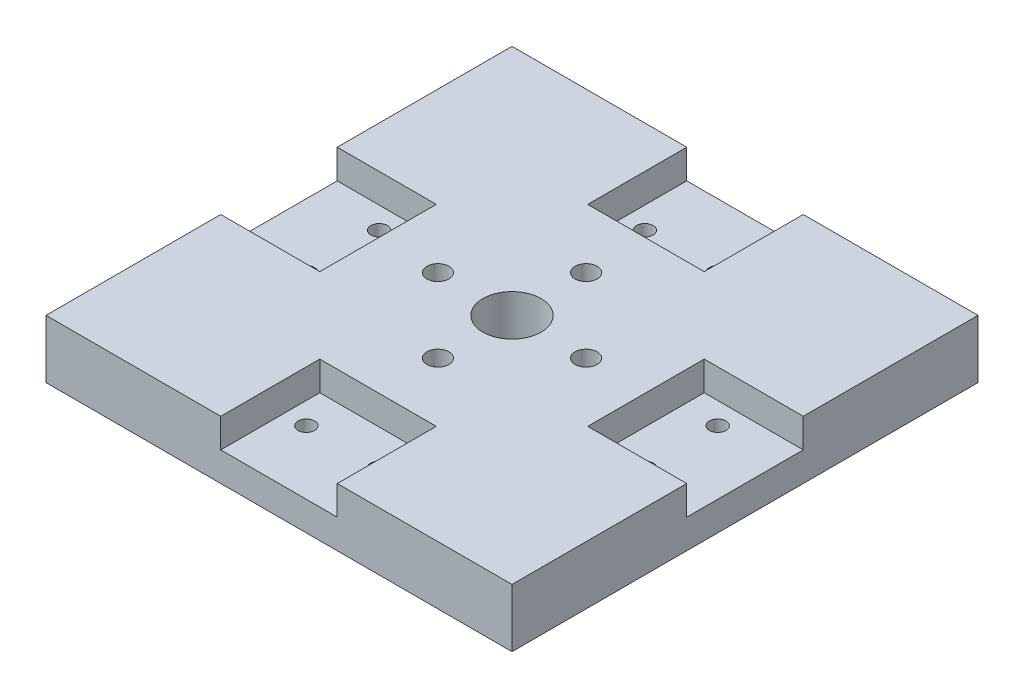
SolidWorks part; units mm, degrees
material "6061 Alloy"
ref_plane "Front Plane" through (0, 0, 0) normal (0, 0, 1) x (1, 0, 0)
ref_plane "Top Plane" through (0, 0, 0) normal (0, 1, 0) x (1, 0, 0)
ref_plane "Right Plane" through (0, 0, 0) normal (1, 0, 0) x (0, 0, -1)
sketch "Sketch1" plane through (0, 0, 0) normal (0, 1, 0) x (1, 0, 0)
  line L1 (0, 0) -> (101.6, 0)
  line L2 (0, 0) -> (0, 101.6)
  line L3 (0, 101.6) -> (101.6, 101.6)
  line L4 (101.6, 0) -> (101.6, 101.6)
  dimension "D1" = 101.6
  dimension "D2" = 101.6
extrude "Boss-Extrude1" add sketch "Sketch1" along normal blind 12.7
sketch "Sketch2" plane through (0, 12.7, 0) normal (0, 1, 0) x (1, 0, 0)
  line L0 (101.6, 101.6) -> (0, 101.6) construction
  line L1 (38.1, 101.6) -> (63.5, 101.6)
  line L2 (38.1, 101.6) -> (38.1, 80.01)
  line L3 (38.1, 80.01) -> (63.5, 80.01)
  line L4 (63.5, 101.6) -> (63.5, 80.01)
  line L5 (0, 101.6) -> (0, 0) construction
  line L6 (0, 63.5) -> (21.59, 63.5)
  line L7 (0, 63.5) -> (0, 38.1)
  line L8 (0, 38.1) -> (21.59, 38.1)
  line L9 (21.59, 63.5) -> (21.59, 38.1)
  line L10 (0, 0) -> (101.6, 0) construction
  line L11 (38.1, 0) -> (63.5, 0)
  line L12 (38.1, 0) -> (38.1, 21.59)
  line L13 (38.1, 21.59) -> (63.5, 21.59)
  line L14 (63.5, 0) -> (63.5, 21.59)
  line L15 (101.6, 0) -> (101.6, 101.6) construction
  line L16 (101.6, 63.5) -> (80.01, 63.5)
  line L17 (101.6, 63.5) -> (101.6, 38.1)
  line L18 (101.6, 38.1) -> (80.01, 38.1)
  line L19 (80.01, 63.5) -> (80.01, 38.1)
  dimension "D1" = 38.1
  dimension "D2" = 25.4
  dimension "D3" = 25.4
  dimension "D4" = 38.1
  dimension "D5" = 25.4
  dimension "D6" = 38.1
  dimension "D7" = 25.4
  dimension "D8" = 38.1
  dimension "D9" = 21.59
  dimension "D10" = 21.59
  dimension "D11" = 21.59
  dimension "D12" = 21.59
extrude "Cut-Extrude1" cut sketch "Sketch2" against normal blind 6.35
sketch "Sketch3" plane through (0, 12.7, 0) normal (0, 1, 0) x (1, 0, 0)
  line L0 (38.1, 101.6) -> (0, 101.6) construction
  line L1 (20.6375, 80.9625) -> (80.9625, 80.9625)
  line L2 (20.6375, 80.9625) -> (20.6375, 20.6375)
  line L3 (20.6375, 20.6375) -> (80.9625, 20.6375)
  line L4 (80.9625, 80.9625) -> (80.9625, 20.6375)
  line L5 (0, 38.1) -> (0, 0) construction
  circle A0 centre (34.6507, 50.8) radius 2.4
  circle A1 centre (50.8, 66.9493) radius 2.4
  circle A2 centre (66.9493, 50.8) radius 2.4
  circle A3 centre (50.8, 34.6507) radius 2.4
  dimension "D5" = 4.8
  dimension "D6" = 4.8
  dimension "D7" = 4.8
  dimension "D8" = 4.8
  dimension "D1" = 60.325
  dimension "D2" = 60.325
  dimension "D3" = 20.6375
  dimension "D4" = 20.6375
  dimension "D9" = 14.0132
  dimension "D10" = 14.0132
  dimension "D11" = 14.0132
  dimension "D12" = 14.0132
  dimension "D13" = 30.1625
  dimension "D14" = 30.1625
  dimension "D15" = 30.1625
  dimension "D16" = 30.1625
extrude "Cut-Extrude2" cut sketch "Sketch3" against normal through all contours A2 | A1 | A0 | A3
sketch "Sketch4" plane through (0, 6.35, 0) normal (0, 1, 0) x (1, 0, 0)
  line L0 (0, 63.5) -> (0, 38.1) construction
  line L1 (63.5, 101.6) -> (38.1, 101.6) construction
  line L2 (101.6, 38.1) -> (101.6, 63.5) construction
  line L3 (38.1, 0) -> (63.5, 0) construction
  line L4 (0, 38.1) -> (21.59, 38.1) construction
  line L5 (38.1, 21.59) -> (38.1, 0) construction
  line L6 (80.01, 38.1) -> (101.6, 38.1) construction
  line L7 (63.5, 80.01) -> (63.5, 101.6) construction
  circle A0 centre (87.7062, 58.7375) radius 1.8034
  circle A1 centre (87.7062, 42.8625) radius 1.8034
  circle A2 centre (58.7375, 87.7062) radius 1.8034
  circle A3 centre (42.8625, 87.7062) radius 1.8034
  circle A4 centre (13.8938, 58.7375) radius 1.8034
  circle A5 centre (13.8938, 42.8625) radius 1.8034
  circle A6 centre (42.8625, 13.8938) radius 1.8034
  circle A7 centre (58.7375, 13.8938) radius 1.8034
  dimension "D1" = 3.6068
  dimension "D2" = 3.6068
  dimension "D3" = 3.6068
  dimension "D4" = 3.6068
  dimension "D5" = 3.6068
  dimension "D6" = 3.6068
  dimension "D7" = 3.6068
  dimension "D8" = 3.6068
  dimension "D9" = 13.8938
  dimension "D10" = 13.8938
  dimension "D11" = 13.8938
  dimension "D12" = 13.8938
  dimension "D13" = 13.8938
  dimension "D14" = 13.8938
  dimension "D15" = 13.8938
  dimension "D16" = 13.8938
  dimension "D17" = 15.875
  dimension "D18" = 4.7625
  dimension "D19" = 4.7625
  dimension "D20" = 15.875
  dimension "D21" = 4.7625
  dimension "D22" = 15.875
  dimension "D23" = 4.7625
  dimension "D24" = 15.875
extrude "Cut-Extrude3" cut sketch "Sketch4" against normal through all
sketch "Sketch5" plane through (0, 12.7, 0) normal (0, 1, 0) x (1, 0, 0)
  line L0 (101.6, 101.6) -> (63.5, 101.6) construction
  line L1 (101.6, 38.1) -> (101.6, 63.5) construction
  circle A0 centre (50.8, 50.8) radius 6.35
  dimension "D1" = 12.7
  dimension "D2" = 50.8
  dimension "D3" = 50.8
extrude "Cut-Extrude4" cut sketch "Sketch5" against normal through all
equation "\"hinge_hole\"= 0.142in"
equation "\"D1@Sketch4\"=\"hinge_hole\""
equation "\"D2@Sketch4\"=\"hinge_hole\""
equation "\"D3@Sketch4\"=\"hinge_hole\""
equation "\"D4@Sketch4\"=\"hinge_hole\""
equation "\"D5@Sketch4\"=\"hinge_hole\""
equation "\"D6@Sketch4\"=\"hinge_hole\""
equation "\"D7@Sketch4\"=\"hinge_hole\""
equation "\"D8@Sketch4\"=\"hinge_hole\""
equation "\"hinge_hole_dist\" = 0.297 + 0.25"
equation "\"D9@Sketch4\"=\"hinge_hole_dist\""
equation "\"D10@Sketch4\"=\"hinge_hole_dist\""
equation "\"D11@Sketch4\"=\"hinge_hole_dist\""
equation "\"D12@Sketch4\"=\"hinge_hole_dist\""
equation "\"D13@Sketch4\"=\"hinge_hole_dist\""
equation "\"D14@Sketch4\"=\"hinge_hole_dist\""
equation "\"D15@Sketch4\"=\"hinge_hole_dist\""
equation "\"D16@Sketch4\"=\"hinge_hole_dist\""
equation "\"hinge_hole_sep\"= 0.625"
equation "\"hinge_hole_from_wall\"= ( 1 - \"hinge_hole_sep\" ) / 2"
equation "\"D17@Sketch4\"=\"hinge_hole_sep\""
equation "\"D18@Sketch4\"=\"hinge_hole_from_wall\""
equation "\"D19@Sketch4\"=\"hinge_hole_from_wall\""
equation "\"D20@Sketch4\"=\"hinge_hole_sep\""
equation "\"D21@Sketch4\"=\"hinge_hole_from_wall\""
equation "\"D22@Sketch4\"=\"hinge_hole_sep\""
equation "\"D23@Sketch4\"=\"hinge_hole_from_wall\""
equation "\"D24@Sketch4\"=\"hinge_hole_sep\""
equation "\"D9@Sketch2\"=\"hinge_hole_dist\" + (0.6-0.297)"
equation "\"D12@Sketch2\"=\"hinge_hole_dist\" + (0.6-0.297)"
equation "\"D11@Sketch2\"=\"hinge_hole_dist\" + (0.6-0.297)"
equation "\"D10@Sketch2\"=\"hinge_hole_dist\" + (0.6-0.297)"
